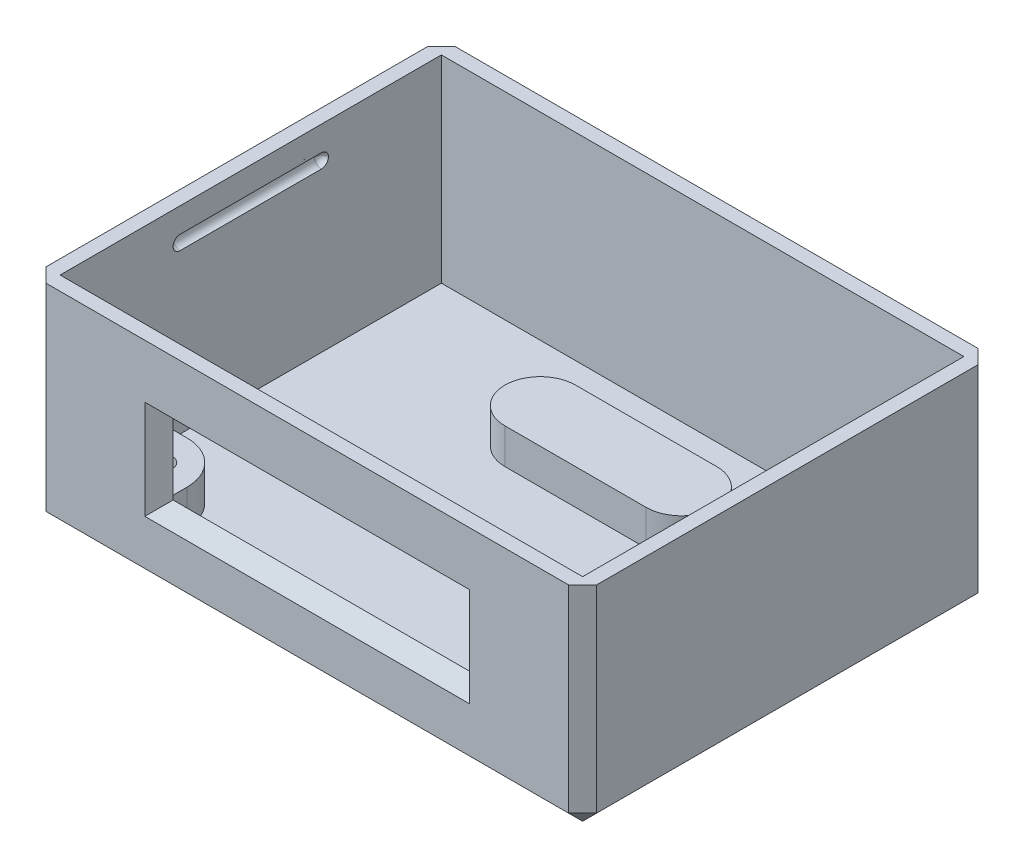
SolidWorks part; units mm, degrees
ref_plane "Front" through (0, 0, 0) normal (0, 0, 1) x (1, 0, 0)
ref_plane "Top" through (0, 0, 0) normal (0, 1, 0) x (1, 0, 0)
ref_plane "Right" through (0, 0, 0) normal (1, 0, 0) x (0, 0, -1)
sketch "Sketch1" plane through (0, 0, 0) normal (0, 1, 0) x (1, 0, 0)
  line L1 (-19.5, -14.5) -> (19.5, -14.5)
  line L2 (-19.5, -14.5) -> (-19.5, 14.5)
  line L3 (-19.5, 14.5) -> (19.5, 14.5)
  line L4 (19.5, -14.5) -> (19.5, 14.5)
  line L5 (-19.5, -14.5) -> (19.5, 14.5) construction
  line L6 (-19.5, 14.5) -> (19.5, -14.5) construction
  point P0 (0, 0)
  dimension "D1" = 39
  dimension "D2" = 29
extrude "Boss-Extrude1" add sketch "Sketch1" along normal blind 15
sketch "Sketch2" plane through (0, 15, 0) normal (0, 1, 0) x (1, 0, 0)
  line L8 (18.5, -13.5) -> (18.5, 13.5)
  line L9 (18.5, 13.5) -> (-18.5, 13.5)
  line L10 (-18.5, 13.5) -> (-18.5, -13.5)
  line L11 (-18.5, -13.5) -> (18.5, -13.5)
  line L12 (18.5, -13.5) -> (18.5, 13.5)
  line L13 (18.5, 13.5) -> (-18.5, 13.5)
  line L14 (-18.5, 13.5) -> (-18.5, -13.5)
  line L15 (-18.5, -13.5) -> (18.5, -13.5)
  dimension "D1" = 1
extrude "Cut-Extrude1" cut sketch "Sketch2" against normal offset from surface (14 mm away) 1 up to face at (0, 0, 0)
chamfer "Chamfer1" distance 1 angle 45 8 edges at (0, 0, -14.5) (-19.5, 7.5, -14.5) (-19.5, 0, 0) (-19.5, 7.5, 14.5) (0, 0, 14.5) (19.5, 7.5, 14.5) (19.5, 0, 0) (19.5, 7.5, -14.5)
sketch "Sketch3" plane through (0, 0, 14.5) normal (0, 0, 1) x (1, 0, 0)
  line L1 (-10.5, 5.2) -> (10.5, 5.2)
  line L2 (-10.5, 5.2) -> (-10.5, 10.2)
  line L3 (-10.5, 10.2) -> (10.5, 10.2)
  line L4 (10.5, 5.2) -> (10.5, 10.2)
  line L5 (-10.5, 5.2) -> (10.5, 10.2) construction
  line L6 (-10.5, 10.2) -> (10.5, 5.2) construction
  line L7 (10.5, 5.2) -> (-10.5, 5.2) construction
  line L8 (10.5, 14.1) -> (10.5, 5.2) construction
  point P0 (0, 7.7)
  dimension "D1" = 5
extrude "Cut-Extrude2" cut sketch "Sketch3" against normal up to next
sketch "Sketch4" plane through (-18.5, 0, 0) normal (1, 0, 0) x (0, 0, -1)
  line L0 (-13.5, 15) -> (13.5, 15) construction
  line L1 (-5.5, 12.25) -> (5.5, 12.25)
  line L2 (-5.5, 12.25) -> (-5.5, 13.25)
  line L3 (-5.5, 13.25) -> (5.5, 13.25)
  line L4 (5.5, 12.25) -> (5.5, 13.25)
  point P6 (0, 15)
  point P7 (0, 12.25)
  dimension "D1" = 1.75
  dimension "D2" = 11
  dimension "D3" = 1
extrude "Cut-Extrude3" cut sketch "Sketch4" against normal blind 0.5
fillet "Fillet1" radius 0.5 2 edges at (-19, 13.25, 0) (-19, 12.25, 0)
mirror "Mirror2" about plane through (0, 0, 0) normal (1, 0, 0) of "Cut-Extrude3", "Fillet1"
sketch "Sketch5" plane through (0, 1, 0) normal (0, 1, 0) x (1, 0, 0)
  line L1 (-18.5, -13.5) -> (-12.5, -13.5)
  line L2 (-18.5, -13.5) -> (-18.5, -7.5)
  line L3 (-18.5, -7.5) -> (-15.5, -7.5)
  line L4 (-12.5, -13.5) -> (-12.5, -10.5)
  line L9 (-14.9, -10.65) -> (-14.9, -13.5) construction
  line L10 (-5, 7) -> (5, 7) construction
  line L11 (-5, 9.5) -> (5, 9.5)
  line L12 (-5, 4.5) -> (5, 4.5)
  line L13 (0, -50) -> (0, 50) construction
  line L14 (14.9, -10.65) -> (14.9, -13.5) construction
  line L15 (18.5, 13.5) -> (-18.5, 13.5) construction
  line L16 (12.5, -13.5) -> (12.5, -10.5)
  line L17 (18.5, -7.5) -> (15.5, -7.5)
  line L18 (18.5, -13.5) -> (18.5, -7.5)
  line L19 (18.5, -13.5) -> (12.5, -13.5)
  circle A0 centre (-14.9, -9.9) radius 0.75
  arc A4 (-5, 9.5) -> (-5, 4.5) centre (-5, 7) ccw
  arc A5 (5, 4.5) -> (5, 9.5) centre (5, 7) ccw
  circle A6 centre (-14.9, -9.9) radius 1 construction
  arc A7 (-15.5, -7.5) -> (-12.5, -10.5) centre (-15.5, -10.5) cw
  arc A8 (15.5, -7.5) -> (12.5, -10.5) centre (15.5, -10.5) ccw
  circle A9 centre (14.9, -9.9) radius 0.75
  point P10 (0, 7)
  point P29 (-7.5, 7)
  point P32 (7.5, 7)
  dimension "D1" = 3
  dimension "D2" = 1.5
  dimension "D3" = 3
  dimension "D4" = 4
  dimension "D5" = 5
  dimension "D6" = 15
extrude "Boss-Extrude2" add sketch "Sketch5" along normal blind 2.5
chamfer "Chamfer2" distance 1 angle 45 4 edges at (-10.5, 7.7, 14.5) (0, 5.2, 14.5) (10.5, 7.7, 14.5) (0, 10.2, 14.5)
